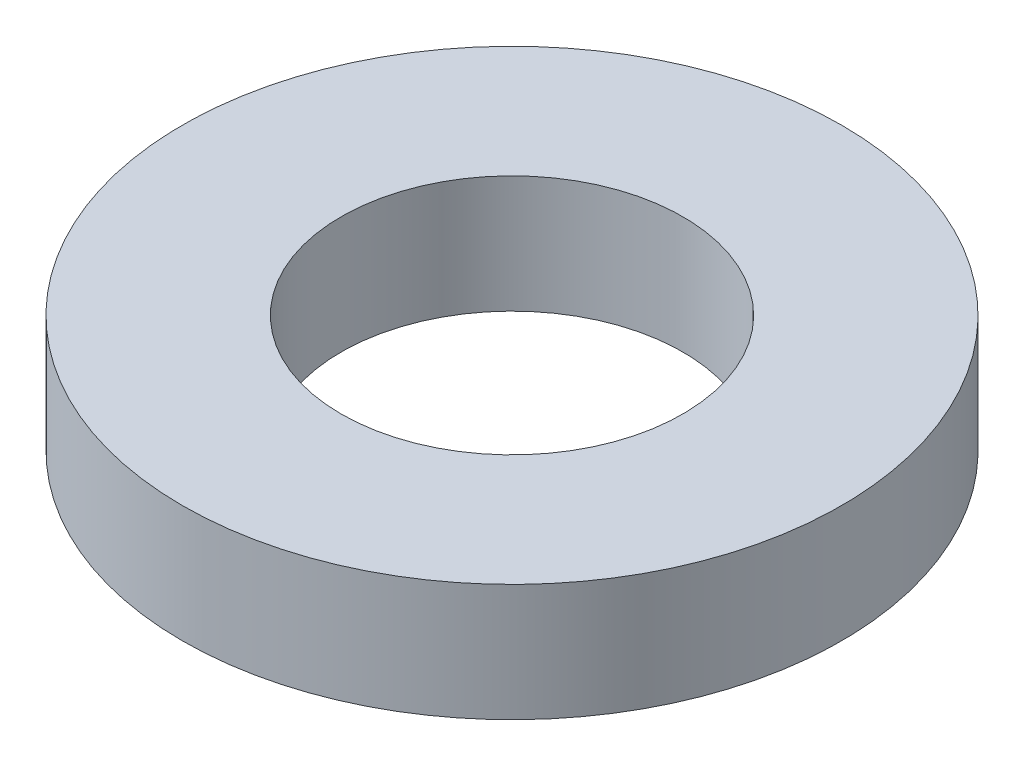
SolidWorks part; units mm, degrees
ref_plane "Front Plane" through (0, 0, 0) normal (0, 0, 1) x (1, 0, 0)
ref_plane "Top Plane" through (0, 0, 0) normal (0, 1, 0) x (1, 0, 0)
ref_plane "Right Plane" through (0, 0, 0) normal (1, 0, 0) x (0, 0, -1)
sketch "Sketch1" plane through (0, 0, 0) normal (0, 1, 0) x (1, 0, 0)
  circle A0 centre (0, 0) radius 67.5
  dimension "FLANGE_OD" = 135
extrude "Boss-Extrude1" add sketch "Sketch1" along normal blind 24
sketch "Sketch2" plane through (0, 0, 0) normal (0, 1, 0) x (1, 0, 0)
  circle A0 centre (0, 0) radius 35
  dimension "BORE_D" = 70
extrude "Cut-Extrude1" cut sketch "Sketch2" along normal through all
sketch "Sketch3" plane through (0, 24, 0) normal (0, 1, 0) x (1, 0, 0)
  circle A0 centre (0, 0) radius 25.7019 construction
  circle A1 centre (-25.7019, 0) radius 2.0438
  dimension "BOLT_D" = 4.0876
  dimension "BOLT_PCD" = 51.4038
extrude "Cut-Extrude2" cut sketch "Sketch3" against normal blind 18.5634 rebuild error yes
pattern_circular "CirPattern1" count 4 over 360 rebuild error yes
